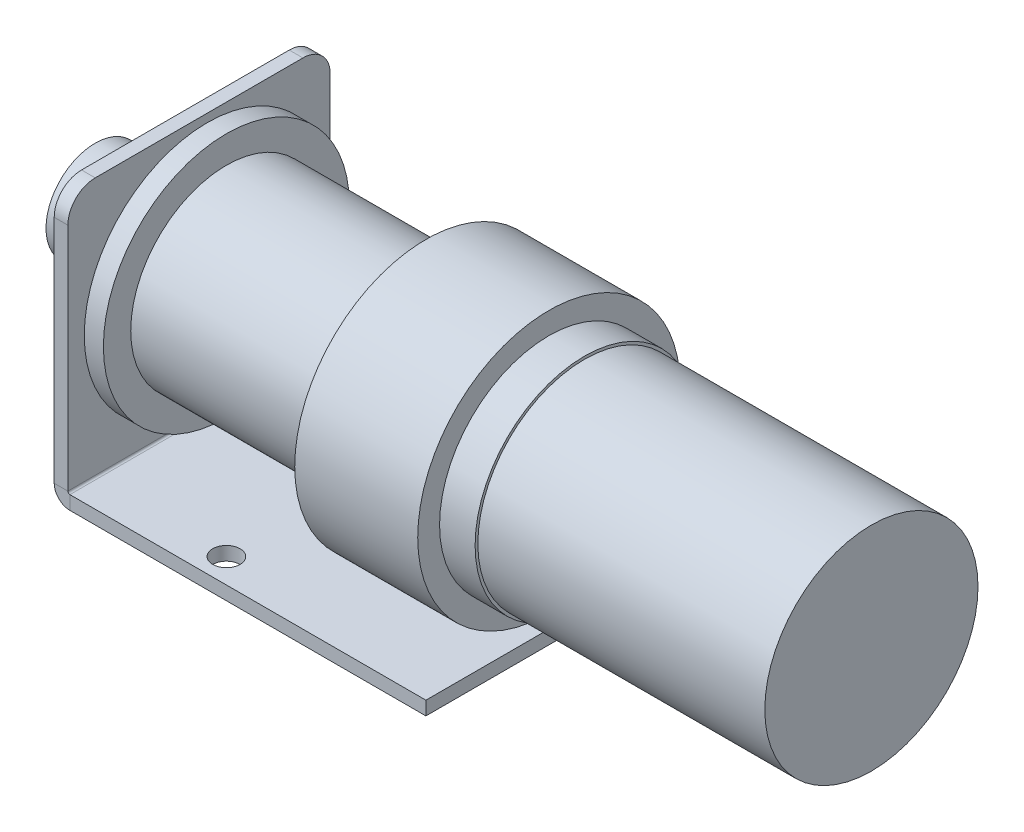
SolidWorks part; units mm, degrees
note: '?' marks a value the reader was unsure of. The reader was unsure of these and kept them because the rebuilt part matched: bend radius of "Основание1".
material "AISI 1020"
ref_plane "Спереди" through (0, 0, 0) normal (0, 0, 1) x (1, 0, 0)
ref_plane "Сверху" through (0, 0, 0) normal (0, 1, 0) x (1, 0, 0)
ref_plane "Справа" through (0, 0, 0) normal (1, 0, 0) x (0, 0, -1)
sketch "Эскиз1" plane through (0, 0, 0) normal (0, 0, 1) x (1, 0, 0)
  line L0 (-1759.0292, 0) -> (86192.4325, 0) construction
  line L1 (-121, 0) -> (-121, 18)
  line L2 (-121, 18) -> (-111, 18)
  line L3 (-111, 18) -> (-111, 7.5)
  line L4 (-111, 7.5) -> (-80, 7.5)
  line L5 (-80, 7.5) -> (-80, 45)
  line L6 (-80, 45) -> (-73, 45)
  line L7 (-73, 45) -> (-73, 35)
  line L8 (-73, 35) -> (0, 35)
  line L9 (0, 35) -> (0, 48)
  line L10 (0, 48) -> (45, 48)
  line L11 (45, 48) -> (45, 40)
  line L12 (45, 40) -> (58, 40)
  line L13 (58, 40) -> (58, 39)
  line L14 (58, 39) -> (163, 39)
  line L15 (163, 39) -> (163, 0)
  line L16 (163, 0) -> (-121, 0)
  dimension "D1" = 36
  dimension "D2" = 15
  dimension "D3" = 90
  dimension "D4" = 70
  dimension "D5" = 96
  dimension "D6" = 80
  dimension "D7" = 78
  dimension "D8" = 105
  dimension "D9" = 13
  dimension "D10" = 45
  dimension "D11" = 73
  dimension "D12" = 7
  dimension "D13" = 31
  dimension "D14" = 10
revolve "Повернуть1" add sketch "Эскиз1" angle 360 about L0
sketch "Эскиз2" plane through (0, 0, 0) normal (0, 0, 1) x (1, 0, 0)
  line L0 (-83, 45) -> (-83, -50)
  line L1 (-83, -50) -> (48, -50)
  line L2 (-80, 45) -> (-80, -45) construction
  line L3 (-73, 45) -> (-80, 45) construction
  dimension "D1" = 3
  dimension "D2" = 131
  dimension "D3" = 95
base flange "Базовая кромка1" sketch "Эскиз2" end condition mid plane depth 96 reverse direction no thickness 5 reverse thickness direction no bend radius 0.74
bend "Основание1" bend radius 0.74 bend angle 90 parameters "D5"=1
fillet "Скругление1" radius 10 2 edges at (-85.5, 45, 48) (-85.5, 45, -48)
sketch "Эскиз7" plane through (0, -55, 0) normal (0, -1, 0) x (1, 0, 0)
  line L0 (-34, 44) -> (-34, -44) construction
  line L1 (-29, 39) -> (48, 39) construction
  line L2 (48, 48) -> (48, -48) construction
  circle A0 centre (-34, 39) radius 5
  circle A1 centre (-34, -39) radius 5
  point P13 (-34, 0)
  dimension "D1" = 10
  dimension "D2" = 77
  dimension "D3" = 88
extrude "Вырез-Вытянуть1" cut sketch "Эскиз7" against normal blind 10
ref_axis "Ось1" through (-34, -50, 39) along (0, -1, 0)?
ref_plane "Плоскость1" through (-36.5, 0, 0) normal (1, 0, 0) x (0, 0, -1)
sketch "Сгиб-Линии1" plane through (0, 0, 0) normal (0, 1, 0) x (1, 0, 0)
sketch "Граничная рамка1" plane through (0, 0, 0) normal (0, 1, 0) x (1, 0, 0)
sheet metal parameters "Листовой металл4" thickness 5 parameters "D1"=0.74
flat pattern "Развертка4" [suppressed]
sketch "Сгиб-Линии2" plane through (0, 0, 0) normal (0, 1, 0) x (1, 0, 0)
sketch "Граничная рамка2" [suppressed] plane through (0, 0, 0) normal (0, 1, 0) x (1, 0, 0)
bend of the flat pattern "Плоское состояние-<Основание1>1"
sheet metal parameters "Листовой металл5" thickness 5 parameters "D1"=0.74
flat pattern "Развертка4" [suppressed]
sketch "Сгиб-Линии2" plane through (0, 0, 0) normal (0, 1, 0) x (1, 0, 0)
sketch "Граничная рамка2" [suppressed] plane through (0, 0, 0) normal (0, 1, 0) x (1, 0, 0)
bend of the flat pattern "Плоское состояние-<Основание1>1"
